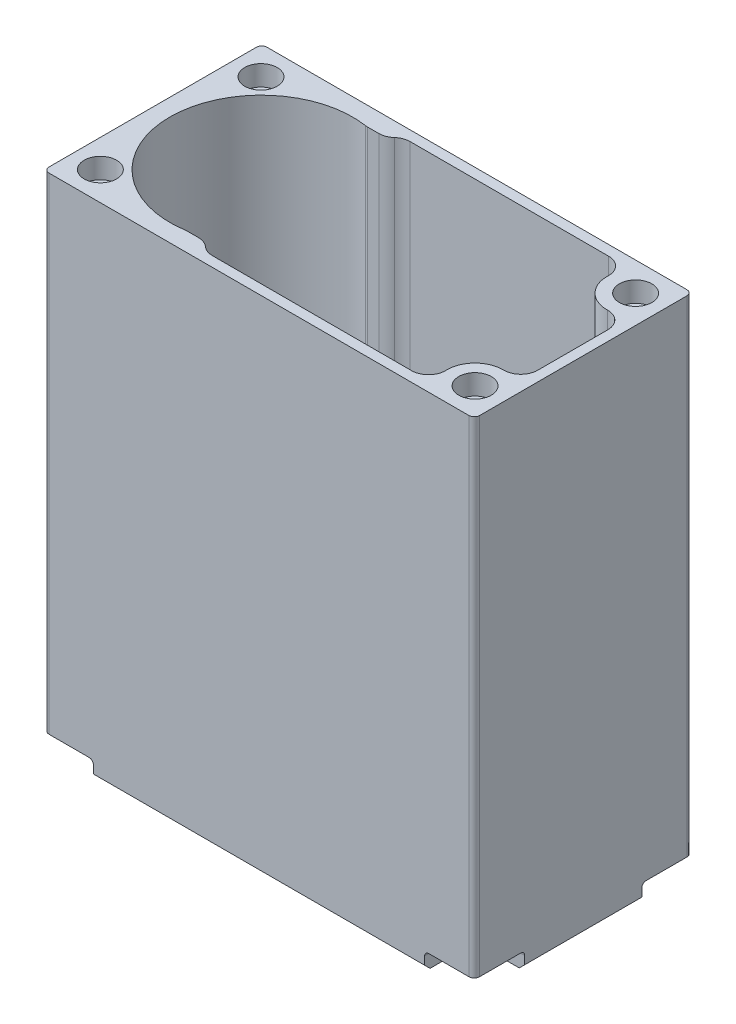
SolidWorks part; units mm, degrees
ref_plane "Front Plane" through (0, 0, 0) normal (0, 0, 1) x (1, 0, 0)
ref_plane "Top Plane" through (0, 0, 0) normal (0, 1, 0) x (1, 0, 0)
ref_plane "Right Plane" through (0, 0, 0) normal (1, 0, 0) x (0, 0, -1)
sketch "Sketch1" plane through (0, 0, 0) normal (0, 1, 0) x (1, 0, 0)
  line L1 (-20.193, 10.2235) -> (20.193, 10.2235)
  line L2 (-20.193, 10.2235) -> (-20.193, -10.2235)
  line L3 (-20.193, -10.2235) -> (20.193, -10.2235)
  line L4 (20.193, 10.2235) -> (20.193, -10.2235)
  line L5 (-20.193, 10.2235) -> (20.193, -10.2235) construction
  line L6 (-20.193, -10.2235) -> (20.193, 10.2235) construction
  point P0 (0, 0)
  dimension "D1" = 40.386
  dimension "D2" = 20.447
extrude "Boss-Extrude1" add sketch "Sketch1" along normal blind 47.244
fillet "Fillet1" radius 0.508 4 edges at (20.193, 23.622, 10.2235) (20.193, 23.622, -10.2235) (-20.193, 23.622, -10.2235) (-20.193, 23.622, 10.2235)
chamfer "Chamfer1" distance 0.508 angle 45 8 edges at (0, 0, -10.2235) (-20.0442, 0, -10.0747) (20.0442, 0, -10.0747) (-20.193, 0, 0) (20.193, 0, 0) (-20.0442, 0, 10.0747) (20.0442, 0, 10.0747) (0, 0, 10.2235)
hole_wizard "#2 Clearance Hole1" positions "Sketch4" profile "Sketch5" hole size "#2" standard "ANSI Inch" end condition up to next
sketch "Sketch4" plane through (0, 47.244, 0) normal (0, 1, 0) x (1, 0, 0)
  line L1 (-17.5704, 7.5311) -> (17.5704, 7.5311)
  line L2 (-17.5704, 7.5311) -> (-17.5704, -7.5311)
  line L3 (-17.5704, -7.5311) -> (17.5704, -7.5311)
  line L4 (17.5704, 7.5311) -> (17.5704, -7.5311)
  line L5 (-17.5704, 7.5311) -> (17.5704, -7.5311) construction
  line L6 (-17.5704, -7.5311) -> (17.5704, 7.5311) construction
  point P2 (17.5704, -7.5311)
  point P81 (-17.5704, 7.5311)
  point P82 (-17.5704, -7.5311)
  point P83 (17.5704, 7.5311)
  point P97 (0, 0)
  dimension "D1" = 15.0622
  dimension "D2" = 35.1409
sketch "Sketch5" plane through (17.5704, 47.244, 7.5311) normal (1, 0, 0) x (0, 0, 1)
  line L0 (0, 0) -> (0, 47.244)
  line L1 (0, 47.244) -> (1.1303, 47.244)
  line L2 (1.1303, 47.244) -> (1.1303, 0)
  line L5 (1.1303, 0) -> (0, 0)
  line L11 (0, -6.35) -> (0, 107.95) construction
  dimension "Thru Hole Dia." = 2.2606
  dimension "Thru Hole Depth" = 47.244
sketch "Sketch6" plane through (0, 47.244, 0) normal (0, 1, 0) x (1, 0, 0)
  circle A0 centre (-10.0147, 0) radius 8.5725
  circle A2 centre (-17.5704, 7.5311) radius 1.1303 construction
  dimension "D1" = 17.145
  dimension "D2" = 10.668
extrude "Cut-Extrude1" cut sketch "Sketch6" against normal offset from surface (45.974 mm away) 1.27 up to face at (17.5704, 0, 8.6614)
sketch "Sketch8" plane through (0, 47.244, 0) normal (0, 1, 0) x (1, 0, 0)
  circle A0 centre (-17.5704, -7.5311) radius 1.524
  circle A1 centre (-17.5704, 7.5311) radius 1.524
  circle A2 centre (17.5704, 7.5311) radius 1.524
  circle A3 centre (17.5704, -7.5311) radius 1.524
  dimension "D1" = 3.048
extrude "Cut-Extrude2" cut sketch "Sketch8" against normal blind 1.905
sketch "Sketch10" plane through (0, 47.244, 0) normal (0, 1, 0) x (1, 0, 0)
  line L0 (-8.6142, 8.4573) -> (-8.6142, -8.4573)
  line L1 (-8.6142, -8.4573) -> (-6.7092, -8.4573)
  line L2 (-6.7092, -8.4573) -> (-6.7092, -9.271)
  line L3 (-6.7092, -9.271) -> (15.6082, -9.271)
  line L5 (19.2416, -5.5099) -> (19.2416, 5.4201)
  line L7 (15.5158, 9.271) -> (-6.7092, 9.271)
  line L8 (-6.7092, 9.271) -> (-6.7092, 8.4573)
  line L9 (-6.7092, 8.4573) -> (-8.6142, 8.4573)
  line L10 (20.193, -9.7155) -> (20.193, 9.7155) construction
  line L11 (19.685, 10.2235) -> (-19.685, 10.2235) construction
  line L12 (4.4033, 9.271) -> (4.4033, 10.2235) construction
  line L14 (19.2416, -0.0449) -> (20.193, 0) construction
  circle A0 centre (-10.0147, 0) radius 8.5725 construction
  circle A1 centre (-10.0147, 0) radius 8.5725 construction
  arc A2 (15.5158, 9.271) -> (19.2416, 5.4201) centre (17.5704, 7.5311) ccw
  arc A3 (19.2416, -5.5099) -> (15.6082, -9.271) centre (17.5704, -7.5311) ccw
  circle M17 centre (-10.0147, 0) radius 8.5725
  dimension "D1" = 22.225
  dimension "D3" = 18.542
  dimension "D4" = 1.905
extrude "Cut-Extrude4" cut sketch "Sketch10" against normal up to surface (45.974 mm away) contours A3 L5 A2 L7 L8 L9 L1 L2 L3 M17 region at (6.9584, 47.244, 0.0089) up to face at (-10.0147, 1.27, 8.5725)
fillet "Fillet3" radius 1.5875 8 edges at (-6.7092, 24.257, -9.271) (-8.6142, 24.257, -8.4573) (-8.6142, 24.257, 8.4573) (-6.7092, 24.257, 9.271) (15.6082, 24.257, 9.271) (19.2416, 24.257, 5.5099) (19.2416, 24.257, -5.4201) (15.5158, 24.257, -9.271)
fillet "Fillet6" radius 1.5875 2 edges at (-6.7092, 24.257, 8.4573) (-6.7092, 24.257, -8.4573)
fillet "Fillet4" radius 0.381 18 edges at (-8.6088, 1.27, 8.4618) (-8.6088, 1.27, -8.4618) (-5.8914, 1.27, -9.1658) (-5.8914, 1.27, 9.1658) (4.02, 1.27, 9.271) (14.5058, 1.27, 8.7855) (15.7009, 1.27, 5.6919) (18.7654, 1.27, 4.4555) (19.2416, 1.27, 0.0349) (18.7656, 1.27, -4.3855) (15.6514, 1.27, -5.6427) (14.4356, 1.27, -8.7859) (-18.5872, 1.27, 0) (3.9851, 1.27, -9.271) (-7.9674, 1.27, 8.4573) (-7.9674, 1.27, -8.4573) (-6.8773, 1.27, -8.5625) (-6.8773, 1.27, 8.5625)
sketch "Sketch9" plane through (0, 0, 0) normal (0, -1, 0) x (1, 0, 0)
  line L0 (-17.5704, -5.4991) -> (-20.193, -5.4991)
  line L1 (-15.5384, 7.5311) -> (-15.5384, 10.2235)
  line L2 (-15.5384, -7.5311) -> (-15.5384, -10.2235)
  line L4 (19.685, 10.2235) -> (-19.685, 10.2235)
  line L5 (20.193, -9.7155) -> (20.193, 9.7155)
  line L6 (-19.685, -10.2235) -> (19.685, -10.2235)
  line L7 (-20.193, 9.7155) -> (-20.193, -9.7155)
  line L8 (19.685, 10.2235) -> (15.5384, 10.2235)
  line L9 (20.193, -9.7155) -> (20.193, -5.4991)
  line L10 (-19.685, -10.2235) -> (-15.5384, -10.2235)
  line L11 (-20.193, 9.7155) -> (-20.193, 5.4991)
  line L12 (-17.5704, 5.4991) -> (-20.193, 5.4991)
  line L13 (-20.193, 5.4991) -> (-17.5704, 5.4991)
  line L14 (17.5704, 5.4991) -> (20.193, 5.4991)
  line L16 (15.5384, 7.5311) -> (15.5384, 10.2235)
  line L17 (15.5384, 10.2235) -> (15.5384, 7.5311)
  line L18 (15.5384, -7.5311) -> (15.5384, -10.2235)
  line L19 (20.193, 5.4991) -> (20.193, 9.7155)
  line L20 (17.5704, -5.4991) -> (20.193, -5.4991)
  line L21 (15.5384, -10.2235) -> (19.685, -10.2235)
  line L22 (-20.193, -5.4991) -> (-20.193, -9.7155)
  line L24 (-15.5384, 10.2235) -> (-19.685, 10.2235)
  arc A0 (-15.5384, -7.5311) -> (-17.5704, -5.4991) centre (-17.5704, -7.5311) ccw
  arc A1 (-17.5704, 5.4991) -> (-15.5384, 7.5311) centre (-17.5704, 7.5311) ccw
  arc A2 (15.5384, 7.5311) -> (17.5704, 5.4991) centre (17.5704, 7.5311) ccw
  arc A3 (17.5704, -5.4991) -> (15.5384, -7.5311) centre (17.5704, -7.5311) ccw
  arc A8 (20.193, 9.7155) -> (19.685, 10.2235) centre (19.685, 9.7155) ccw
  arc A9 (19.685, -10.2235) -> (20.193, -9.7155) centre (19.685, -9.7155) ccw
  arc A10 (-20.193, -9.7155) -> (-19.685, -10.2235) centre (-19.685, -9.7155) ccw
  arc A11 (-19.685, 10.2235) -> (-20.193, 9.7155) centre (-19.685, 9.7155) ccw
  arc A12 (20.193, 9.7155) -> (19.685, 10.2235) centre (19.685, 9.7155) ccw
  arc A13 (19.685, -10.2235) -> (20.193, -9.7155) centre (19.685, -9.7155) ccw
  arc A14 (-20.193, -9.7155) -> (-19.685, -10.2235) centre (-19.685, -9.7155) ccw
  arc A15 (-19.685, 10.2235) -> (-20.193, 9.7155) centre (-19.685, 9.7155) ccw
  circle M13 centre (17.5704, 7.5311) radius 1.1303
  circle M14 centre (-17.5704, -7.5311) radius 1.1303
  circle M15 centre (-17.5704, 7.5311) radius 1.1303
  circle M16 centre (17.5704, -7.5311) radius 1.1303
  line M17 (-19.685, 9.7155) -> (-19.685, -9.7155)
  line M18 (-19.685, -9.7155) -> (19.685, -9.7155)
  line M19 (19.685, -9.7155) -> (19.685, 9.7155)
  line M20 (19.685, 9.7155) -> (-19.685, 9.7155)
  dimension "D1" = 4.064
  dimension "D2" = 0
extrude "Cut-Extrude5" cut sketch "Sketch9" against normal blind 1.651 contours L12 A1 L1 M20 M17 M15 | L24 A15 L11 L12 L1 M17 M20 | L2 A0 L0 M17 M18 M14 | L22 A14 L10 L2 L0 M18 M17 | L16 A2 L14 M19 M20 M13 | L19 A12 L8 L16 L14 M20 M19 | L20 A3 L18 M18 M19 M16 | L21 A13 L9 L20 L18 M19 M18 region at (-16.1754, 0, -6.1361) region at (-19.7513, 0, -7.6073) region at (-19.6259, 0, 7.6073) region at (-19.939, 0, 5.5654) region at (17.6117, 0, -9.7818) region at (15.5976, 0, -8.6233) region at (17.6117, 0, 9.6564) region at (15.6048, 0, 9.9695)
fillet "Fillet5" radius 0.381 12 edges at (15.5384, 1.651, 8.8773) (16.1336, 1.651, 6.0943) (15.5384, 1.651, -8.8773) (16.1336, 1.651, -6.0943) (-15.5384, 1.651, -8.8773) (-18.8817, 1.651, -5.4991) (-18.8817, 1.651, 5.4991) (-15.5384, 1.651, 8.8773) (18.8817, 1.651, 5.4991) (18.8817, 1.651, -5.4991) (-16.1336, 1.651, -6.0943) (-16.1336, 1.651, 6.0943)
sketch "Sketch12" plane through (9.9695, 0, -10.2235) normal (0, 0, 1) x (1, 0, 0)
  line L1 (3.1596, 7.0573) -> (3.1596, 17.6159) construction
  line L2 (3.1596, 17.6159) -> (-5.9844, 22.8952) construction
  line L3 (-5.9844, 22.8952) -> (-15.1284, 17.6159) construction
  line L4 (-15.1284, 17.6159) -> (-15.1284, 7.0573) construction
  line L5 (-15.1284, 7.0573) -> (-5.9844, 1.778) construction
  line L6 (-5.9844, 1.778) -> (3.1596, 7.0573) construction
  line L7 (3.3238, 1.27) -> (-15.2926, 1.27) construction
  line L8 (3.3238, 1.27) -> (-15.2926, 1.27)
  circle A0 centre (-5.9844, 12.3366) radius 9.144 construction
  circle A1 centre (-5.9844, 12.3366) radius 7.62
  point P15 (-5.9844, 1.27)
  dimension "D1" = 15.24
  dimension "D2" = 0.508
  dimension "D3" = 18.288
extrude "Cut-Extrude8" cut sketch "Sketch12" along normal up to next contours A1
equation "\"D1@Boss-Extrude1\"=.86+1"
